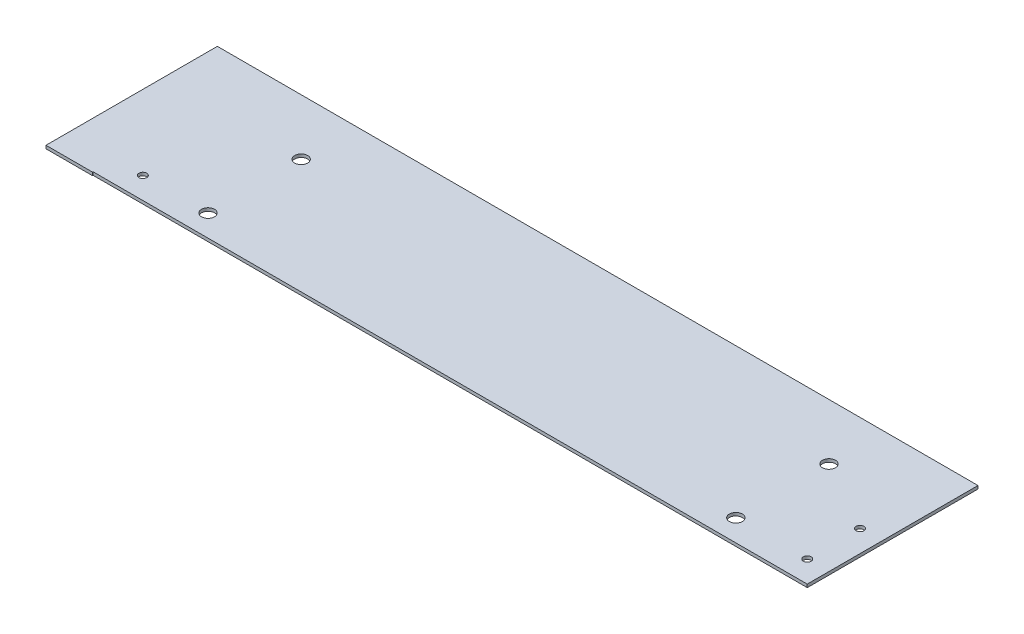
SolidWorks part; units mm, degrees
ref_plane "正面" through (0, 0, 0) normal (0, 0, 1) x (1, 0, 0)
ref_plane "平面" through (0, 0, 0) normal (0, 1, 0) x (1, 0, 0)
ref_plane "右側面" through (0, 0, 0) normal (1, 0, 0) x (0, 0, -1)
sketch "ｽｹｯﾁ1" plane through (0, 0, 0) normal (0, 0, 1) x (1, 0, 0)
  line L1 (0, 0) -> (230, 0)
  line L2 (0, 0) -> (0, 1)
  line L3 (0, 1) -> (230, 1)
  line L4 (230, 0) -> (230, 1)
  dimension "D1" = 1
  dimension "D2" = 230
extrude "ﾎﾞｽ - 押し出し1" add sketch "ｽｹｯﾁ1" along normal blind 15
hole_wizard "M3x0.5 ねじ穴1" positions "ｽｹｯﾁ2" profile "ｽｹｯﾁ3" tap size "M3x0.5" standard "JIS" end condition through all
sketch "ｽｹｯﾁ2" plane through (0, 0, 0) normal (0, -1, 0) x (-1, 0, 0)
  line L0 (0, -15) -> (0, 0) construction
  line L1 (-230, -15) -> (-230, 0) construction
  line L2 (-55, 0) -> (55, 0) construction
  point P0 (-9, -8)
  point P2 (-223, -8)
  point P9 (-230, -7.5)
  dimension "D1" = 9
  dimension "D2" = 7
  dimension "D3" = 8
  dimension "D4" = 8
sketch "ｽｹｯﾁ3" plane through (9, 0, 8) normal (1, 0, 0) x (0, 0, -1)
  line L0 (0, 0) -> (0, 1)
  line L1 (0, 1) -> (1.25, 1)
  line L2 (1.25, 1) -> (1.25, 0)
  line L5 (1.25, 0) -> (0, 0)
  line L11 (0, -6.35) -> (0, 107.95) construction
  dimension "次ｻｰﾌｪｽまでのねじ下穴ﾄﾞﾘﾙ直径" = 2.5
  dimension "次ｻｰﾌｪｽまでのねじ下穴ﾄﾞﾘﾙの深さ" = 1
cosmetic thread "穴のねじ山1" parameters "D2"=3
cosmetic thread "穴のねじ山2" parameters "D2"=3
hole_wizard "M5x0.8 ねじ穴1" positions "ｽｹｯﾁ4" profile "ｽｹｯﾁ5" tap size "M5x0.8" standard "JIS" end condition through all
sketch "ｽｹｯﾁ4" plane through (0, 1, 0) normal (0, 1, 0) x (1, 0, 0)
  line L0 (230, -15) -> (230, 0) construction
  line L1 (0, -15) -> (0, 0) construction
  line L2 (230, -15) -> (0, -15) construction
  point P0 (30, -8)
  point P2 (200, -8)
  dimension "D1" = 30
  dimension "D2" = 30
  dimension "D3" = 7
  dimension "D4" = 7
cosmetic thread "穴のねじ山3" parameters "D2"=5
cosmetic thread "穴のねじ山4" parameters "D2"=5
sketch "ｽｹｯﾁ5" plane through (30, 1, 8) normal (1, 0, 0) x (0, 0, 1)
  line L0 (0, 0) -> (0, 1)
  line L1 (0, 1) -> (2.1, 1)
  line L2 (2.1, 1) -> (2.1, 0)
  line L5 (2.1, 0) -> (0, 0)
  line L11 (0, -6.35) -> (0, 107.95) construction
  dimension "次ｻｰﾌｪｽまでのねじ下穴ﾄﾞﾘﾙ直径" = 4.2
  dimension "次ｻｰﾌｪｽまでのねじ下穴ﾄﾞﾘﾙの深さ" = 1
sketch "ｽｹｯﾁ10" plane through (0, 0, 0) normal (0, 0, -1) x (-1, 0, 0)
  line L0 (-230, 1) -> (0, 1) construction
  line L1 (-210, 1) -> (-190, 1)
  line L2 (-210, 1) -> (-210, 0)
  line L3 (-210, 0) -> (-190, 0)
  line L4 (-190, 1) -> (-190, 0)
  line L5 (0, 0) -> (-230, 0) construction
  line L6 (-230, 0) -> (-230, 1) construction
  point P10 (-230, 0.5)
  dimension "D1" = 20
  dimension "D2" = 20
extrude "ﾎﾞｽ - 押し出し3" add sketch "ｽｹｯﾁ10" along normal blind 40
sketch "ｽｹｯﾁ11" plane through (0, 0, 0) normal (0, 0, -1) x (-1, 0, 0)
  line L0 (0, 1) -> (0, 0) construction
  line L1 (0, 1) -> (-40, 1)
  line L2 (0, 1) -> (0, 0)
  line L3 (0, 0) -> (-40, 0)
  line L4 (-40, 1) -> (-40, 0)
  line L5 (0, 0) -> (-190, 0) construction
  dimension "D1" = 40
extrude "ﾎﾞｽ - 押し出し4" add sketch "ｽｹｯﾁ11" along normal blind 40
hole_wizard "M5x0.8 ねじ穴3" positions "ｽｹｯﾁ12" profile "ｽｹｯﾁ13" tap size "M5x0.8" standard "JIS" end condition through all
sketch "ｽｹｯﾁ12" plane through (0, 1, 0) normal (0, 1, 0) x (1, 0, 0)
  line L0 (40, 40) -> (40, 0) construction
  line L1 (190, 40) -> (190, 0) construction
  circle A0 centre (30, -8) radius 2.1 construction
  circle A1 centre (200, -8) radius 2.1 construction
  point P0 (30, 22)
  point P2 (200, 22)
  dimension "D2" = 30
  dimension "D1" = 10
  dimension "D3" = 30
  dimension "D4" = 10
sketch "ｽｹｯﾁ13" plane through (30, 1, -22) normal (1, 0, 0) x (0, 0, 1)
  line L0 (0, 0) -> (0, 1)
  line L1 (0, 1) -> (2.1, 1)
  line L2 (2.1, 1) -> (2.1, 0)
  line L5 (2.1, 0) -> (0, 0)
  line L11 (0, -6.35) -> (0, 107.95) construction
  dimension "次ｻｰﾌｪｽまでのねじ下穴ﾄﾞﾘﾙ直径" = 4.2
  dimension "次ｻｰﾌｪｽまでのねじ下穴ﾄﾞﾘﾙの深さ" = 1
cosmetic thread "穴のねじ山11" parameters "D2"=5
cosmetic thread "穴のねじ山12" parameters "D2"=5
sketch "ｽｹｯﾁ15" plane through (40, 0, 0) normal (1, 0, 0) x (0, 0, -1)
  line L0 (0, 1) -> (0, 0) construction
  line L1 (0, 1) -> (40, 1)
  line L2 (0, 1) -> (0, 0)
  line L3 (0, 0) -> (40, 0)
  line L4 (40, 1) -> (40, 0)
extrude "ﾎﾞｽ - 押し出し6" add sketch "ｽｹｯﾁ15" along normal blind 150
sketch "ｽｹｯﾁ16" plane through (210, 0, 0) normal (1, 0, 0) x (0, 0, -1)
  line L1 (40, 1) -> (0, 1)
  line L2 (40, 1) -> (40, 0)
  line L3 (40, 0) -> (0, 0)
  line L4 (0, 1) -> (0, 0)
extrude "ﾎﾞｽ - 押し出し7" add sketch "ｽｹｯﾁ16" along normal blind 20
sketch "ｽｹｯﾁ17" plane through (230, 0, 0) normal (1, 0, 0) x (0, 0, -1)
  line L0 (-15, 0) -> (40, 0) construction
  line L1 (40, 1) -> (-15, 1)
  line L2 (40, 1) -> (40, 0)
  line L3 (40, 0) -> (-15, 0)
  line L4 (-15, 1) -> (-15, 0)
sketch "ｽｹｯﾁ18" plane through (0, 0, 0) normal (-1, 0, 0) x (0, 0, 1)
  line L0 (-40, 0) -> (-40, 1) construction
  line L1 (-40, 1) -> (15.1887, 1)
  line L2 (-40, 1) -> (-40, 0)
  line L3 (-40, 0) -> (15.1887, 0)
  line L4 (15.1887, 1) -> (15.1887, 0)
extrude "ﾎﾞｽ - 押し出し9" add sketch "ｽｹｯﾁ18" along normal blind 15
hole_wizard "M3x0.5 ねじ穴2" positions "ｽｹｯﾁ19" profile "ｽｹｯﾁ20" tap size "M3x0.5" standard "JIS"
sketch "ｽｹｯﾁ19" plane through (0, 0, 0) normal (0, -1, 0) x (-1, 0, 0)
  line L0 (-230, -15) -> (-230, 40) construction
  circle A0 centre (-223, -8) radius 1.25 construction
  point P0 (-223, 9)
  dimension "D1" = 7
  dimension "D2" = 17
sketch "ｽｹｯﾁ20" plane through (223, 0, -9) normal (1, 0, 0) x (0, 0, -1)
  line L0 (0, 0) -> (0, 9.2511)
  line L1 (0, 9.2511) -> (1.25, 8.5)
  line L2 (1.25, 8.5) -> (1.25, 0)
  line L5 (1.25, 0) -> (0, 0)
  line L10 (0, 9.2511) -> (-1.25, 8.5) construction
  line L11 (0, -6.35) -> (0, 107.95) construction
  dimension "ねじ下穴ﾄﾞﾘﾙ直径" = 2.5
  dimension "ねじ下穴ﾄﾞﾘﾙの深さ" = 8.5
  dimension "ﾄﾞﾘﾙ角度" = 118
